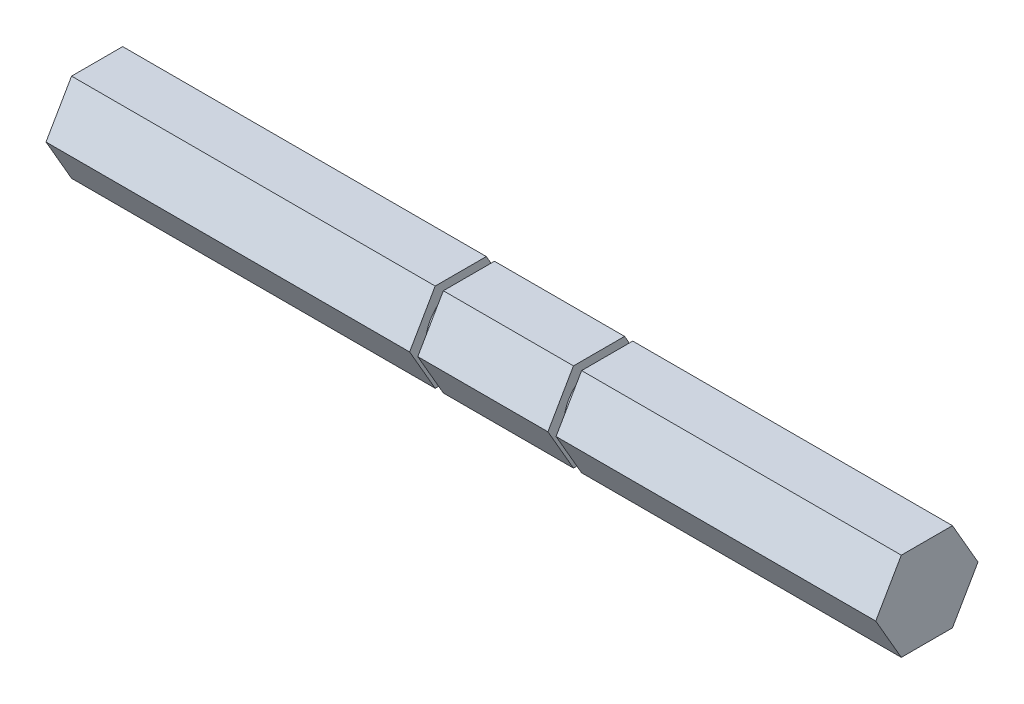
SolidWorks part; units mm, degrees
note: '?' marks a value the reader was unsure of.
material "7075-T6 (SN)"
ref_plane "Front Plane" through (0, 0, 0) normal (0, 0, 1) x (1, 0, 0)
ref_plane "Top Plane" through (0, 0, 0) normal (0, 1, 0) x (1, 0, 0)
ref_plane "Right Plane" through (0, 0, 0) normal (1, 0, 0) x (0, 0, -1)
sketch "Sketch2" plane through (0, 0, 0) normal (1, 0, 0) x (0, 0, -1)
  line L1 (7.3323, 0) -> (3.6662, 6.35)
  line L2 (3.6662, 6.35) -> (-3.6662, 6.35)
  line L3 (-3.6662, 6.35) -> (-7.3323, 0)
  line L4 (-7.3323, 0) -> (-3.6662, -6.35)
  line L5 (-3.6662, -6.35) -> (3.6662, -6.35)
  line L6 (3.6662, -6.35) -> (7.3323, 0)
  circle A0 centre (0, 0) radius 6.35 construction
  dimension "D1" = 12.7
extrude "Boss-Extrude1" add sketch "Sketch2" along normal mid plane 119
sketch "Sketch5" plane through (0, 0, 0) normal (0, 0, 1) x (1, 0, 0)
  line L0 (0, 0) -> (66.5467, 0) construction
  line L1 (12.4816, 13.9685) -> (13.65, 13.9685)
  line L2 (12.4816, 13.9685) -> (12.4816, 5.0292)
  line L3 (12.4816, 5.0292) -> (13.65, 5.0292)
  line L4 (13.65, 13.9685) -> (13.65, 5.0292)
  line L5 (59.5, 6.35) -> (59.5, 0) construction
  line L6 (-7.35, 13.9685) -> (-7.35, 5.0292)
  line L7 (-7.35, 13.9685) -> (-6.1816, 13.9685)
  line L8 (-6.1816, 13.9685) -> (-6.1816, 5.0292)
  line L9 (-7.35, 5.0292) -> (-6.1816, 5.0292)
  dimension "D1" = 1.1684
  dimension "D2" = 10.0584
  dimension "D3" = 45.85
  dimension "D5" = 21
  dimension "D4" = 2
revolve "Cut-Revolve1" cut sketch "Sketch5" angle 360 about L0
ref_axis "Axis1" through (55.0595, 0, 0) along (-1, 0, 0)?
